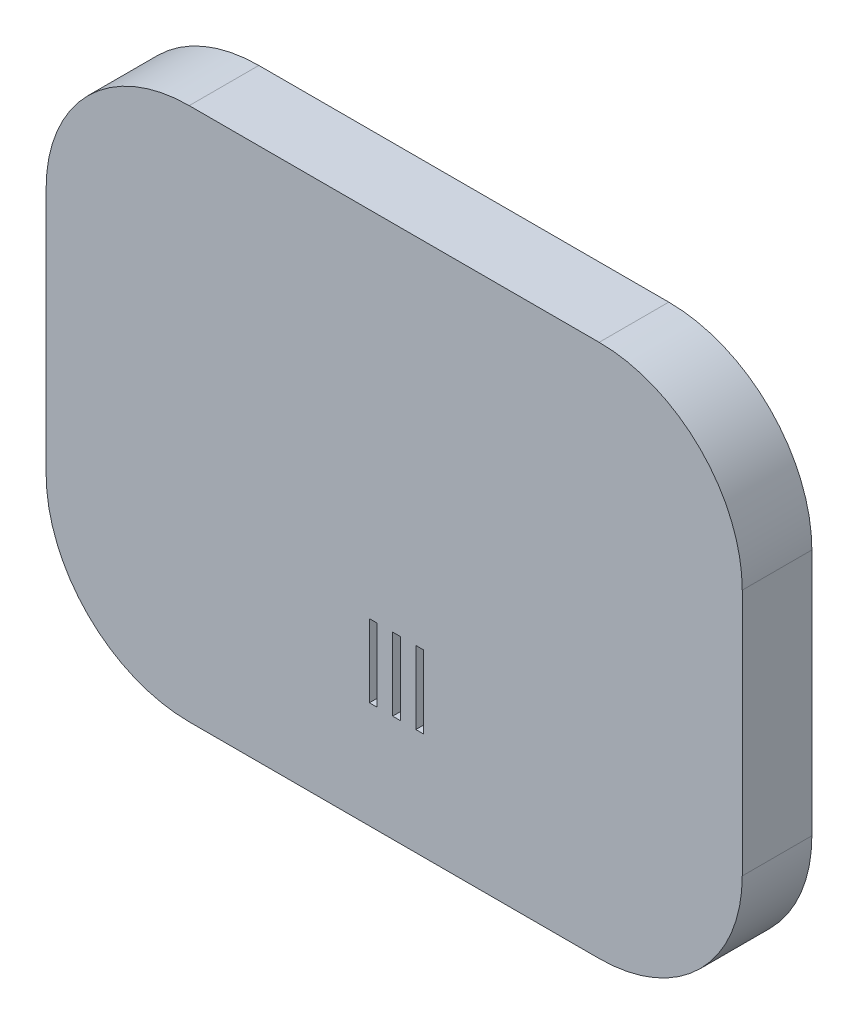
SolidWorks part; units mm, degrees
ref_plane "Front Plane" through (0, 0, 0) normal (0, 0, 1) x (1, 0, 0)
ref_plane "Top Plane" through (0, 0, 0) normal (0, 1, 0) x (1, 0, 0)
ref_plane "Right Plane" through (0, 0, 0) normal (1, 0, 0) x (0, 0, -1)
sketch "Sketch1" plane through (0, 0, 0) normal (0, 0, 1) x (1, 0, 0)
  line L4 (141.0373, 720.5448) -> (194.0373, 720.5448)
  line L5 (212.5373, 739.0448) -> (212.5373, 771.0448)
  line L6 (194.0373, 789.5448) -> (141.0373, 789.5448)
  line L7 (122.5373, 771.0448) -> (122.5373, 739.0448)
  line L8 (141.0373, 720.5448) -> (194.0373, 720.5448)
  line L9 (212.5373, 739.0448) -> (212.5373, 771.0448)
  line L10 (194.0373, 789.5448) -> (141.0373, 789.5448)
  line L11 (122.5373, 771.0448) -> (122.5373, 739.0448)
  arc A4 (122.5373, 739.0448) -> (141.0373, 720.5448) centre (141.0373, 739.0448) ccw
  arc A5 (194.0373, 720.5448) -> (212.5373, 739.0448) centre (194.0373, 739.0448) ccw
  arc A6 (212.5373, 771.0448) -> (194.0373, 789.5448) centre (194.0373, 771.0448) ccw
  arc A7 (141.0373, 789.5448) -> (122.5373, 771.0448) centre (141.0373, 771.0448) ccw
  arc A8 (122.5373, 739.0448) -> (141.0373, 720.5448) centre (141.0373, 739.0448) ccw
  arc A9 (194.0373, 720.5448) -> (212.5373, 739.0448) centre (194.0373, 739.0448) ccw
  arc A10 (212.5373, 771.0448) -> (194.0373, 789.5448) centre (194.0373, 771.0448) ccw
  arc A11 (141.0373, 789.5448) -> (122.5373, 771.0448) centre (141.0373, 771.0448) ccw
  dimension "D1" = 0
extrude "Extrude-Thin1" add sketch "Sketch1" along normal offset from surface (7 mm away) 2 thin offset beyond the face yes thin type one direction reverse wall 1.5
sketch "Sketch2" plane through (0, 0, 7) normal (0, 0, 1) x (1, 0, 0)
  line L4 (122.5373, 771.0448) -> (122.5373, 739.0448)
  line L5 (141.0373, 720.5448) -> (194.0373, 720.5448)
  line L6 (212.5373, 739.0448) -> (212.5373, 771.0448)
  line L7 (194.0373, 789.5448) -> (141.0373, 789.5448)
  line L8 (122.5373, 771.0448) -> (122.5373, 739.0448)
  line L9 (141.0373, 720.5448) -> (194.0373, 720.5448)
  line L10 (212.5373, 739.0448) -> (212.5373, 771.0448)
  line L11 (194.0373, 789.5448) -> (141.0373, 789.5448)
  arc A4 (122.5373, 739.0448) -> (141.0373, 720.5448) centre (141.0373, 739.0448) ccw
  arc A5 (194.0373, 720.5448) -> (212.5373, 739.0448) centre (194.0373, 739.0448) ccw
  arc A6 (212.5373, 771.0448) -> (194.0373, 789.5448) centre (194.0373, 771.0448) ccw
  arc A7 (141.0373, 789.5448) -> (122.5373, 771.0448) centre (141.0373, 771.0448) ccw
  arc A8 (122.5373, 739.0448) -> (141.0373, 720.5448) centre (141.0373, 739.0448) ccw
  arc A9 (194.0373, 720.5448) -> (212.5373, 739.0448) centre (194.0373, 739.0448) ccw
  arc A10 (212.5373, 771.0448) -> (194.0373, 789.5448) centre (194.0373, 771.0448) ccw
  arc A11 (141.0373, 789.5448) -> (122.5373, 771.0448) centre (141.0373, 771.0448) ccw
  dimension "D1" = 0
extrude "Boss-Extrude1" add sketch "Sketch2" along normal blind 2
sketch "Sketch3" plane through (0, 0, 7) normal (0, 0, -1) x (-1, 0, 0)
  line L0 (-211.0373, 739.0448) -> (-124.0373, 739.0448) construction
  arc A0 (-141.0373, 722.0448) -> (-124.0373, 739.0448) centre (-141.0373, 739.0448) ccw construction
  arc A1 (-141.0373, 722.0448) -> (-124.0373, 739.0448) centre (-141.0373, 739.0448) ccw construction
  circle A2 centre (-167.5373, 739.0448) radius 6.05
  dimension "D1" = 12.1
extrude "Extrude-Thin2" add sketch "Sketch3" along normal blind 5 thin thin type one direction wall 1.5
fillet "Fillet1" radius 5 1 edges at (175.0873, 739.0448, 7)
sketch "Sketch4" plane through (0, 0, 7) normal (0, 0, -1) x (-1, 0, 0)
  line L0 (-171.335, 743.7544) -> (-171.335, 734.3352)
  line L1 (-171.335, 734.3352) -> (-170.335, 734.3352)
  line L2 (-170.335, 734.3352) -> (-170.335, 743.7544)
  line L3 (-170.335, 743.7544) -> (-171.335, 743.7544)
  line L4 (-167.335, 734.3352) -> (-167.335, 743.7544)
  line L5 (-168.335, 743.7544) -> (-168.335, 734.3352)
  line L6 (-167.335, 743.7544) -> (-168.335, 743.7544)
  line L7 (-168.335, 734.3352) -> (-167.335, 734.3352)
  line L8 (-164.335, 734.3352) -> (-164.335, 743.7544)
  line L9 (-165.335, 743.7544) -> (-165.335, 734.3352)
  line L10 (-164.335, 743.7544) -> (-165.335, 743.7544)
  line L11 (-165.335, 734.3352) -> (-164.335, 734.3352)
  line L16 (-161.335, 734.3352) -> (-161.335, 743.7544) [skipped]
  line L17 (-162.335, 743.7544) -> (-162.335, 734.3352) [skipped]
  line L18 (-161.335, 743.7544) -> (-162.335, 743.7544) [skipped]
  line L19 (-162.335, 734.3352) -> (-161.335, 734.3352) [skipped]
  circle A0 centre (-167.5373, 739.0448) radius 6.05 construction
  circle A1 centre (-167.5373, 739.0448) radius 6.05 construction
  point P9 (0, 0)
  dimension "D1" = 1
  dimension "D2" = 4
extrude "Cut-Extrude1" cut sketch "Sketch4" against normal through all
